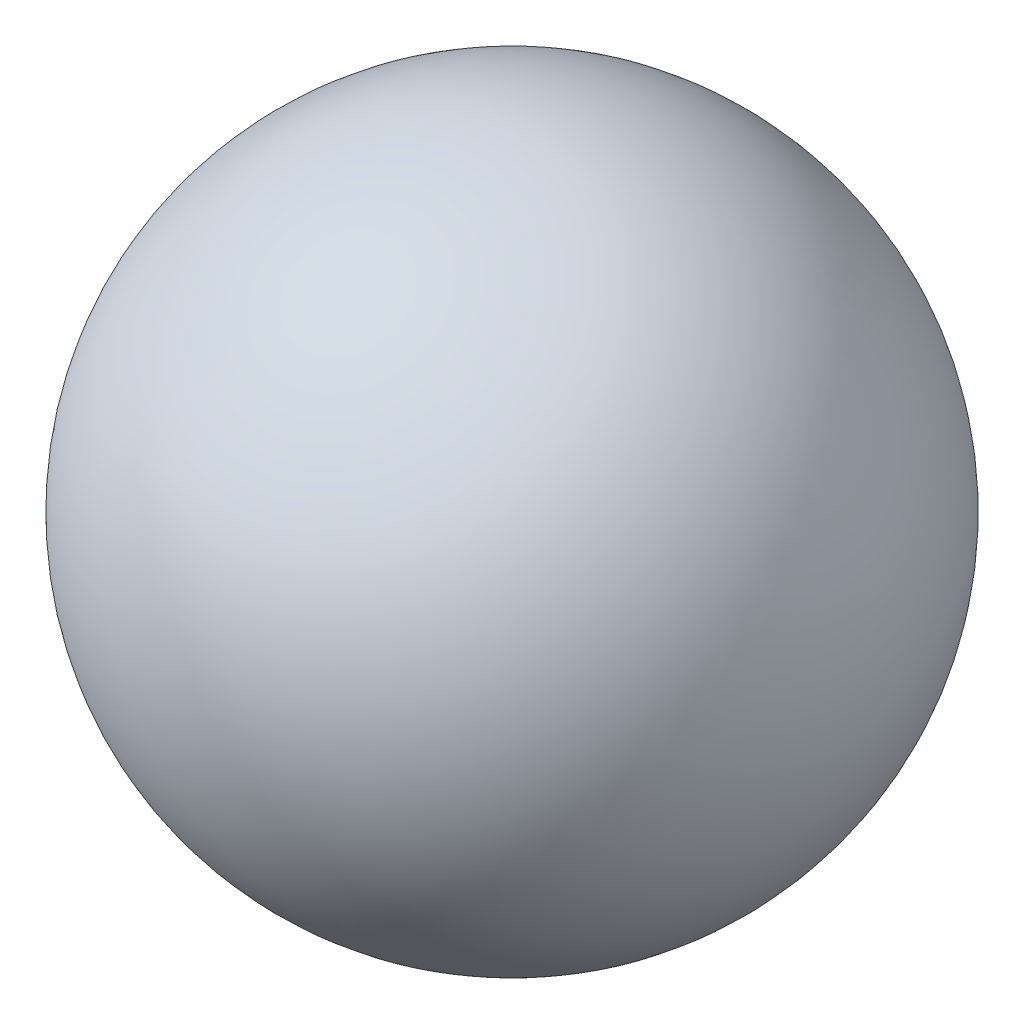
SolidWorks part; units mm, degrees
ref_plane "Front Plane" through (0, 0, 0) normal (0, 0, 1) x (1, 0, 0)
ref_plane "Top Plane" through (0, 0, 0) normal (0, 1, 0) x (1, 0, 0)
ref_plane "Right Plane" through (0, 0, 0) normal (1, 0, 0) x (0, 0, -1)
sketch "Sketch1" plane through (0, 0, 0) normal (0, 0, 1) x (1, 0, 0)
  line L0 (0, 158.75) -> (0, -158.75)
  arc A0 (0, 158.75) -> (0, -158.75) centre (0, 0) cw
  dimension "D1" = 317.5
revolve "Revolve1" add sketch "Sketch1" angle 360 about L0
